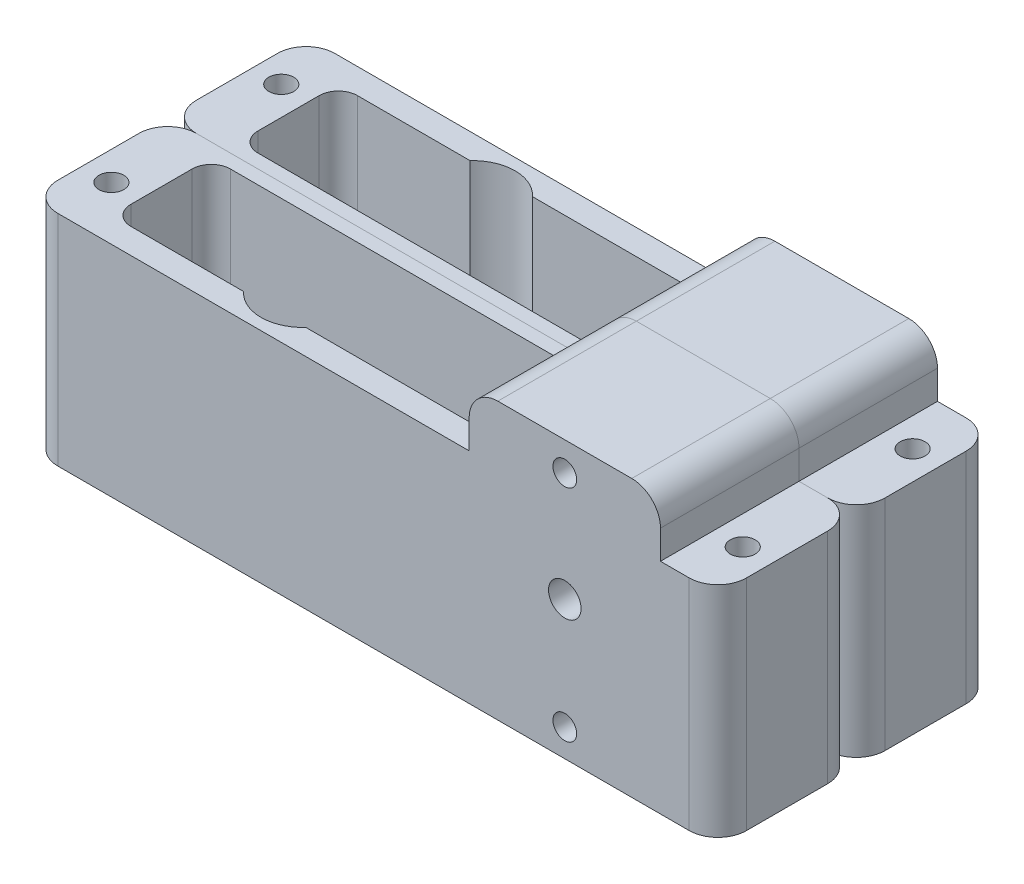
SolidWorks part; units mm, degrees
ref_plane "Front Plane" through (0, 0, 0) normal (0, 0, 1) x (1, 0, 0)
ref_plane "Top Plane" through (0, 0, 0) normal (0, 1, 0) x (1, 0, 0)
ref_plane "Right Plane" through (0, 0, 0) normal (1, 0, 0) x (0, 0, -1)
sketch "Sketch1" plane through (0, 0, 0) normal (0, 0, 1) x (1, 0, 0)
  line L1 (-90, 28.6) -> (90, 28.6)
  line L2 (-90, 28.6) -> (-90, -28.6)
  line L3 (-90, -28.6) -> (90, -28.6)
  line L4 (90, 28.6) -> (90, -28.6)
  line L5 (-90, 28.6) -> (90, -28.6) construction
  line L6 (-90, -28.6) -> (90, 28.6) construction
  line L7 (25, 28.6) -> (75, 28.6)
  line L8 (25, 28.6) -> (25, 43.6)
  line L9 (25, 43.6) -> (75, 43.6)
  line L10 (75, 28.6) -> (75, 43.6)
  point P0 (0, 0)
  dimension "D1" = 180
  dimension "D2" = 57.2
  dimension "D3" = 15
  dimension "D4" = 15
  dimension "D5" = 50
extrude "Boss-Extrude1" add sketch "Sketch1" along normal blind 36.2 contours L4 L1 L2 L3 | L1 L10 L9 L8 region at (0, 0, 0) region at (50, 36.1, 0)
sketch "Sketch2" plane through (0, -28.6, 0) normal (0, -1, 0) x (1, 0, 0)
  line L0 (-90, 36.2) -> (-90, 0) construction
  line L1 (-90, 0) -> (90, 0) construction
  line L2 (90, 36.2) -> (90, 0) construction
  line L3 (-82.5, 14) -> (82.5, 14) construction
  line L4 (-38.0569, 8.3431) -> (-26.7431, 8.3431) construction
  line L5 (-38.0569, 8.3431) -> (-38.0569, 19.6569) construction
  line L6 (-38.0569, 19.6569) -> (-26.7431, 19.6569) construction
  line L7 (-26.7431, 8.3431) -> (-26.7431, 19.6569) construction
  line L8 (-38.0569, 8.3431) -> (-26.7431, 19.6569) construction
  line L9 (-38.0569, 19.6569) -> (-26.7431, 8.3431) construction
  circle A0 centre (-82.5, 14) radius 3.25
  circle A1 centre (82.5, 14) radius 3.25
  circle A2 centre (-32.4, 14) radius 5.75
  circle A3 centre (-32.4, 14) radius 11
  circle A4 centre (-38.0569, 19.6569) radius 1.75
  circle A5 centre (-26.7431, 19.6569) radius 1.75
  circle A6 centre (-26.7431, 8.3431) radius 1.75
  circle A7 centre (-38.0569, 8.3431) radius 1.75
  dimension "D1" = 6.5
  dimension "D4" = 6.5
  dimension "D7" = 11.5
  dimension "D8" = 22
  dimension "D9" = 3.5
  dimension "D11" = 50.1
  dimension "D2" = 7.5
  dimension "D3" = 14
  dimension "D5" = 14
  dimension "D6" = 7.5
  dimension "D10" = 8
extrude "Cut-Extrude1" cut sketch "Sketch2" against normal up to surface (57.2 mm away) contours A0 | A2 | A4 | A5 | A7 | A6 | A1 region at (-82.5, -28.6, 14) region at (-32.4, -28.6, 14) up to face at (-32.5, 28.6, 18.1)
fillet "Fillet1" radius 7.5 4 edges at (90, 0, 0) (90, 0, 36.2) (-90, 0, 0) (-90, 0, 36.2)
sketch "Sketch3" plane through (0, 28.6, 0) normal (0, 1, 0) x (1, 0, 0)
  line L0 (-82.5, -36.2) -> (25, -36.2) construction
  line L1 (-70, -6.5931) -> (25, -6.5931)
  line L2 (-75, -11.5931) -> (-75, -27.6)
  line L3 (-70, -32.6) -> (25, -32.6)
  line L4 (25, -6.5931) -> (25, -32.6)
  line L5 (25, -36.2) -> (25, 0) construction
  circle A0 centre (-38.0569, -8.3431) radius 1.75 construction
  circle A1 centre (-82.5, -14) radius 3.25 construction
  arc A2 (-75, -27.6) -> (-70, -32.6) centre (-70, -27.6) ccw
  arc A3 (-70, -6.5931) -> (-75, -11.5931) centre (-70, -11.5931) ccw
  circle A4 centre (-32.4, -14) radius 11
  circle M6 centre (-26.7431, -8.3431) radius 1.75
  circle M7 centre (-38.0569, -19.6569) radius 1.75
  circle M8 centre (-32.4, -14) radius 5.75
  circle M9 centre (-26.7431, -19.6569) radius 1.75
  circle M10 centre (-38.0569, -8.3431) radius 1.75
  line M16 (25, -36.2) -> (25, 0)
  dimension "D4" = 5
  dimension "D5" = 22
  dimension "D1" = 26.0069
  dimension "D2" = 3.6
  dimension "D3" = 7.5
extrude "Cut-Extrude3" cut sketch "Sketch3" against normal offset from surface (52.2 mm away) 5 contours L1 A4 | L1 A4 M6 M10 M7 M9 M8 | A4 L1 A3 L2 A2 L3 M16 region at (-55.2663, 28.6, 7.6264) region at (-32.4, 28.6, 5.1337) region at (-39.2947, 28.6, 6.88) up to face at (-82.5, -28.6, 10.75)
sketch "Sketch4" plane through (0, 0, 36.2) normal (0, 0, 1) x (1, 0, 0)
  line L0 (-82.5, 28.6) -> (25, 28.6) construction
  line L1 (28.9, 28.6) -> (72.6, 28.6)
  line L2 (28.9, 28.6) -> (28.9, -13.6)
  line L3 (28.9, -13.6) -> (72.6, -13.6)
  line L4 (72.6, 28.6) -> (72.6, -13.6)
  line L5 (50, 7.5) -> (75, 28.6) construction
  line L6 (50, 7.5) -> (25, 28.6) construction
  circle A0 centre (50, 7.5) radius 4.25
  dimension "D5" = 8.5
  dimension "D1" = 42.2
  dimension "D2" = 43.7
  dimension "D3" = 21.1
  dimension "D4" = 21.1
extrude "Cut-Extrude4" cut sketch "Sketch4" against normal blind 33.2
extrude "Cut-Extrude5" cut sketch "Sketch4<3>" against normal up to surface (36.2 mm away) contours A0 up to face at (25, 18.05, 0)
sketch "Sketch4<3>" plane through (0, 0, 36.2) normal (0, 0, 1) x (1, 0, 0) same geometry as "Sketch4"
sketch "Sketch7" plane through (0, 0, 36.2) normal (0, 0, 1) x (1, 0, 0)
  line L0 (72.6, 28.6) -> (28.9, 28.6) construction
  line L2 (50, 36.1) -> (50, -21.4) construction
  line L3 (28.9, 28.6) -> (28.9, -13.6) construction
  circle A0 centre (50, -21.4) radius 3.1
  circle A1 centre (50, 36.1) radius 3.1
  dimension "D1" = 6.2
  dimension "D4" = 6.2
  dimension "D5" = 21.1
  dimension "D2" = 7.5
  dimension "D3" = 57.5
extrude "Cut-Extrude7" cut sketch "Sketch7" against normal up to surface (36.2 mm away) up to face at (54.25, 7.5, 0)
fillet "Fillet2" radius 7.5 2 edges at (75, 43.6, 18.1) (25, 43.6, 18.1)
extrude "Boss-Extrude3" add sketch "Sketch7" against normal blind 22.4
sketch "Sketch8" plane through (0, 0, 3) normal (0, 0, 1) x (1, 0, 0)
  line L1 (28.9, 28.6) -> (72.6, 28.6)
  line L2 (28.9, 28.6) -> (28.9, -13.6)
  line L3 (28.9, -13.6) -> (72.6, -13.6)
  line L4 (72.6, 28.6) -> (72.6, -13.6)
  circle M1 centre (50, 7.5) radius 4.25
  line M2 (28.9, 28.6) -> (28.9, -13.6)
  line M3 (28.9, -13.6) -> (72.6, -13.6)
  line M4 (72.6, -13.6) -> (72.6, 28.6)
  line M5 (72.6, 28.6) -> (28.9, 28.6)
extrude "Boss-Extrude4" add sketch "Sketch8" along normal up to surface (33.2 mm away) contours M5 M2 M3 M4 M1 region at (50.75, 27.9925, 3) up to face at (50.75, 7.5, 36.2)
mirror "Mirror1" about plane through (0, 0, 36.2) normal (0, 0, 1) of bodies 112
